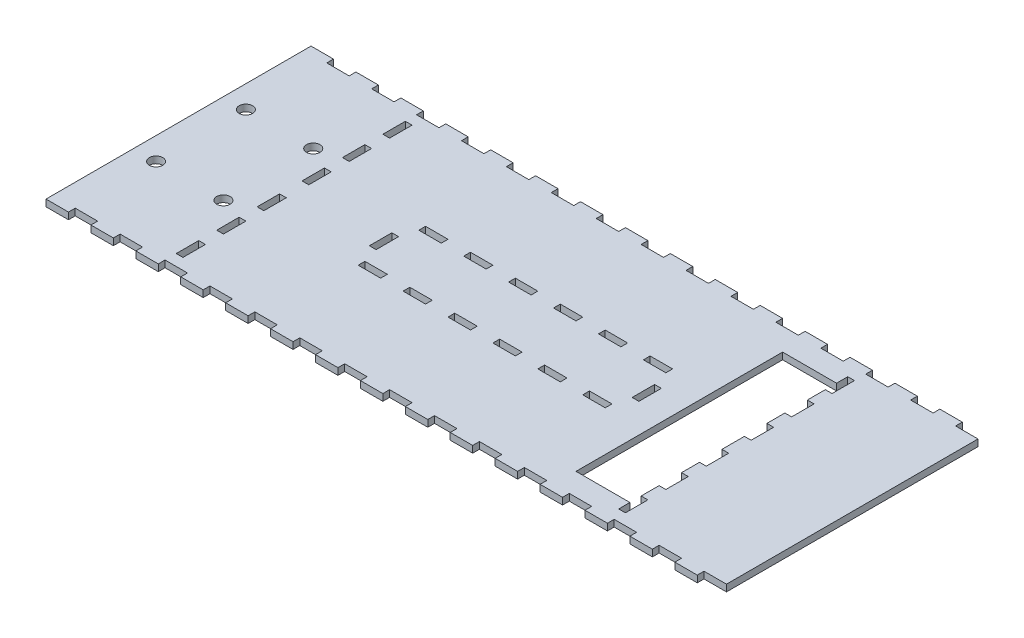
SolidWorks part; units mm, degrees
ref_plane "Front Plane" through (0, 0, 0) normal (0, 0, 1) x (1, 0, 0)
ref_plane "Top Plane" through (0, 0, 0) normal (0, 1, 0) x (1, 0, 0)
ref_plane "Right Plane" through (0, 0, 0) normal (1, 0, 0) x (0, 0, -1)
sketch "Sketch3" plane through (0, 0, 0) normal (0, 1, 0) x (1, 0, 0)
  line L0 (0, 0) -> (-300, 0) construction
  line L1 (-300, -56) -> (-300, 56)
  line L2 (-290, 59) -> (-300, 59)
  line L3 (-290, 56) -> (-290, 59)
  line L4 (-280, 56) -> (-290, 56)
  line L5 (-300, 59) -> (-300, 56)
  line L6 (-270, 59) -> (-280, 59)
  line L7 (-270, 56) -> (-270, 59)
  line L8 (-260, 56) -> (-270, 56)
  line L9 (-280, 59) -> (-280, 56)
  line L10 (-250, 59) -> (-260, 59)
  line L11 (-250, 56) -> (-250, 59)
  line L12 (-240, 56) -> (-250, 56)
  line L13 (-260, 59) -> (-260, 56)
  line L14 (-150, -59) -> (-150, 59) construction
  line L15 (-230, 59) -> (-240, 59)
  line L16 (-230, 56) -> (-230, 59)
  line L17 (-220, 56) -> (-230, 56)
  line L18 (-240, 59) -> (-240, 56)
  line L19 (-210, 59) -> (-220, 59)
  line L20 (-210, 56) -> (-210, 59)
  line L21 (-200, 56) -> (-210, 56)
  line L22 (-10, 59) -> (-20, 59)
  line L23 (0, -56) -> (0, 56)
  line L24 (-10, 56) -> (-10, 59)
  line L25 (-50, -46) -> (-50, 46) construction
  line L26 (-247, 23) -> (-250, 23)
  line L27 (-247, 5) -> (-250, 5)
  line L28 (-247, 48.5) -> (-247, -48.5) construction
  line L29 (-247, 48.5) -> (-223, 48.5) construction
  line L30 (-223, 48.5) -> (-223, -48.5) construction
  line L31 (-210, 15) -> (-90, 15) construction
  line L32 (-90, 15) -> (-90, 5) construction
  line L33 (0, 56) -> (-10, 56)
  line L34 (-220, 59) -> (-220, 56)
  line L35 (-190, 59) -> (-200, 59)
  line L36 (-190, 56) -> (-190, 59)
  line L37 (-180, 56) -> (-190, 56)
  line L38 (-200, 59) -> (-200, 56)
  line L39 (-170, 59) -> (-180, 59)
  line L40 (-170, 56) -> (-170, 59)
  line L41 (-160, 56) -> (-170, 56)
  line L42 (-180, 59) -> (-180, 56)
  line L43 (-150, 59) -> (-160, 59)
  line L44 (-150, 56) -> (-150, 59)
  line L45 (-140, 56) -> (-150, 56)
  line L46 (-160, 59) -> (-160, 56)
  line L47 (-130, 59) -> (-140, 59)
  line L48 (-130, 56) -> (-130, 59)
  line L49 (-120, 56) -> (-130, 56)
  line L50 (-140, 59) -> (-140, 56)
  line L51 (-110, 59) -> (-120, 59)
  line L52 (-110, 56) -> (-110, 59)
  line L53 (-100, 56) -> (-110, 56)
  line L54 (-120, 59) -> (-120, 56)
  line L55 (-90, 59) -> (-100, 59)
  line L56 (-90, 56) -> (-90, 59)
  line L57 (-80, 56) -> (-90, 56)
  line L58 (-100, 59) -> (-100, 56)
  line L59 (-70, 59) -> (-80, 59)
  line L60 (-70, 56) -> (-70, 59)
  line L61 (-60, 56) -> (-70, 56)
  line L62 (-80, 59) -> (-80, 56)
  line L63 (-50, 59) -> (-60, 59)
  line L64 (-50, 56) -> (-50, 59)
  line L65 (-40, 56) -> (-50, 56)
  line L66 (-60, 59) -> (-60, 56)
  line L67 (-30, 59) -> (-40, 59)
  line L68 (-210, -15) -> (-90, -15) construction
  line L69 (-30, 56) -> (-30, 59)
  line L70 (-53, -23) -> (-50, -23)
  line L71 (-20, -59) -> (-20, -56)
  line L72 (-40, -59) -> (-40, -56)
  line L73 (-20, -56) -> (-30, -56)
  line L74 (-30, -56) -> (-30, -59)
  line L75 (-30, -59) -> (-40, -59)
  line L76 (-60, -59) -> (-60, -56)
  line L77 (-40, -56) -> (-50, -56)
  line L78 (-50, -56) -> (-50, -59)
  line L79 (-50, -59) -> (-60, -59)
  line L80 (-80, -59) -> (-80, -56)
  line L81 (-60, -56) -> (-70, -56)
  line L82 (-70, -56) -> (-70, -59)
  line L83 (-70, -59) -> (-80, -59)
  line L84 (-100, -59) -> (-100, -56)
  line L85 (-80, -56) -> (-90, -56)
  line L86 (-90, -56) -> (-90, -59)
  line L87 (-90, -59) -> (-100, -59)
  line L88 (-120, -59) -> (-120, -56)
  line L89 (-100, -56) -> (-110, -56)
  line L90 (-110, -56) -> (-110, -59)
  line L91 (-110, -59) -> (-120, -59)
  line L92 (-140, -59) -> (-140, -56)
  line L93 (-120, -56) -> (-130, -56)
  line L94 (-130, -56) -> (-130, -59)
  line L95 (-130, -59) -> (-140, -59)
  line L96 (-160, -59) -> (-160, -56)
  line L97 (-140, -56) -> (-150, -56)
  line L98 (-150, -56) -> (-150, -59)
  line L99 (-150, -59) -> (-160, -59)
  line L100 (-180, -59) -> (-180, -56)
  line L101 (-160, -56) -> (-170, -56)
  line L102 (-170, -56) -> (-170, -59)
  line L103 (-170, -59) -> (-180, -59)
  line L104 (-200, -59) -> (-200, -56)
  line L105 (-180, -56) -> (-190, -56)
  line L106 (-190, -56) -> (-190, -59)
  line L107 (-190, -59) -> (-200, -59)
  line L108 (-247, -48.5) -> (-223, -48.5) construction
  line L109 (-247, 5) -> (-247, 15)
  line L110 (-220, -59) -> (-220, -56)
  line L111 (0, -56) -> (-10, -56)
  line L112 (-10, -56) -> (-10, -59)
  line L113 (-10, -59) -> (-20, -59)
  line L114 (-200, -56) -> (-210, -56)
  line L115 (-210, -56) -> (-210, -59)
  line L116 (-210, -59) -> (-220, -59)
  line L117 (-240, -59) -> (-240, -56)
  line L118 (-220, -56) -> (-230, -56)
  line L119 (-230, -56) -> (-230, -59)
  line L120 (-230, -59) -> (-240, -59)
  line L121 (-53, -5) -> (-50, -5)
  line L122 (-260, -59) -> (-260, -56)
  line L123 (-240, -56) -> (-250, -56)
  line L124 (-250, -56) -> (-250, -59)
  line L125 (-250, -59) -> (-260, -59)
  line L126 (-280, -59) -> (-280, -56)
  line L127 (-260, -56) -> (-270, -56)
  line L128 (-270, -56) -> (-270, -59)
  line L129 (-270, -59) -> (-280, -59)
  line L130 (-300, -59) -> (-300, -56)
  line L131 (-210, 15) -> (-210, -15) construction
  line L132 (-115, 15) -> (-125, 15)
  line L133 (-90, 5) -> (-93, 5)
  line L134 (-90, 5) -> (-90, -5)
  line L135 (-90, -5) -> (-93, -5)
  line L136 (-93, 5) -> (-93, -5)
  line L137 (-95, 15) -> (-105, 15)
  line L138 (-95, 15) -> (-95, 12)
  line L139 (-95, 12) -> (-105, 12)
  line L140 (-105, 15) -> (-105, 12)
  line L141 (-115, 12) -> (-125, 12)
  line L142 (-125, 15) -> (-125, 12)
  line L143 (-135, 15) -> (-145, 15)
  line L144 (-135, 12) -> (-145, 12)
  line L145 (-145, 15) -> (-145, 12)
  line L146 (-155, 15) -> (-165, 15)
  line L147 (-155, 12) -> (-165, 12)
  line L148 (-165, 15) -> (-165, 12)
  line L149 (-175, 15) -> (-185, 15)
  line L150 (-175, 12) -> (-185, 12)
  line L151 (-185, 15) -> (-185, 12)
  line L152 (-195, 15) -> (-205, 15)
  line L153 (-195, 12) -> (-205, 12)
  line L154 (-205, 15) -> (-205, 12)
  line L155 (-195, 12) -> (-195, 15)
  line L156 (-175, 12) -> (-175, 15)
  line L157 (-155, 12) -> (-155, 15)
  line L158 (-135, 12) -> (-135, 15)
  line L159 (-115, 12) -> (-115, 15)
  line L160 (-207, 5) -> (-207, -5)
  line L161 (-210, -5) -> (-207, -5)
  line L162 (-210, 5) -> (-210, -5)
  line L163 (-210, 5) -> (-207, 5)
  line L164 (-115, -12) -> (-115, -15)
  line L165 (-135, -12) -> (-135, -15)
  line L166 (-155, -12) -> (-155, -15)
  line L167 (-175, -12) -> (-175, -15)
  line L168 (-195, -12) -> (-195, -15)
  line L169 (-205, -15) -> (-205, -12)
  line L170 (-195, -12) -> (-205, -12)
  line L171 (-195, -15) -> (-205, -15)
  line L172 (-185, -15) -> (-185, -12)
  line L173 (-175, -12) -> (-185, -12)
  line L174 (-175, -15) -> (-185, -15)
  line L175 (-165, -15) -> (-165, -12)
  line L176 (-155, -12) -> (-165, -12)
  line L177 (-155, -15) -> (-165, -15)
  line L178 (-145, -15) -> (-145, -12)
  line L179 (-135, -12) -> (-145, -12)
  line L180 (-135, -15) -> (-145, -15)
  line L181 (-125, -15) -> (-125, -12)
  line L182 (-115, -12) -> (-125, -12)
  line L183 (-105, -15) -> (-105, -12)
  line L184 (-95, -12) -> (-105, -12)
  line L185 (-95, -15) -> (-95, -12)
  line L186 (-95, -15) -> (-105, -15)
  line L187 (-115, -15) -> (-125, -15)
  line L188 (-247, 15) -> (-250, 15)
  line L189 (-250, 5) -> (-250, 15)
  line L190 (-247, 23) -> (-247, 33)
  line L191 (-247, 33) -> (-250, 33)
  line L192 (-250, 23) -> (-250, 33)
  line L193 (-247, 41) -> (-250, 41)
  line L194 (-247, 41) -> (-247, 51)
  line L195 (-247, 51) -> (-250, 51)
  line L196 (-250, 41) -> (-250, 51)
  line L197 (-250, -41) -> (-250, -51)
  line L198 (-247, -51) -> (-250, -51)
  line L199 (-247, -41) -> (-247, -51)
  line L200 (-247, -41) -> (-250, -41)
  line L201 (-250, -23) -> (-250, -33)
  line L202 (-247, -33) -> (-250, -33)
  line L203 (-247, -23) -> (-247, -33)
  line L204 (-250, -5) -> (-250, -15)
  line L205 (-247, -15) -> (-250, -15)
  line L206 (-247, -5) -> (-247, -15)
  line L207 (-247, -5) -> (-250, -5)
  line L208 (-247, -23) -> (-250, -23)
  line L209 (-53, -5) -> (-53, -15)
  line L210 (-53, -15) -> (-50, -15)
  line L211 (-50, -5) -> (-50, -15)
  line L212 (-53, -23) -> (-53, -33)
  line L213 (-53, -33) -> (-50, -33)
  line L214 (-50, -23) -> (-50, -33)
  line L215 (-53, -41) -> (-50, -41)
  line L216 (-53, -41) -> (-53, -51)
  line L217 (-53, -51) -> (-50, -51)
  line L218 (-50, -41) -> (-50, -51)
  line L219 (-50, 41) -> (-50, 51)
  line L220 (-53, 51) -> (-50, 51)
  line L221 (-53, 41) -> (-53, 51)
  line L222 (-53, 41) -> (-50, 41)
  line L223 (-50, 23) -> (-50, 33)
  line L224 (-53, 33) -> (-50, 33)
  line L225 (-53, 23) -> (-53, 33)
  line L226 (-50, 5) -> (-50, 15)
  line L227 (-53, 15) -> (-50, 15)
  line L228 (-53, 5) -> (-53, 15)
  line L229 (-53, 5) -> (-50, 5)
  line L230 (-53, 23) -> (-50, 23)
  line L231 (-280, -56) -> (-290, -56)
  line L232 (-290, -56) -> (-290, -59)
  line L233 (-290, -59) -> (-300, -59)
  line L234 (-20, 56) -> (-30, 56)
  line L235 (-40, 59) -> (-40, 56)
  line L236 (-20, 59) -> (-20, 56)
  circle A0 centre (-290, 20) radius 3
  circle A1 centre (-260, 20) radius 3
  circle A2 centre (-260, -20) radius 3
  circle A3 centre (-290, -20) radius 3
  point P80 (-91.5, 0)
  point P82 (-150, 0)
  point P126 (-223, 0)
  point P127 (-250, 0)
  point P129 (-50, 0)
  point P150 (-150, -15)
  point P151 (-150, 15)
  point P183 (-208.5, 0)
  point P212 (-223, 18)
  point P213 (-250, 18)
  point P218 (-223, 36)
  point P219 (-250, 36)
  point P233 (-250, -36)
  point P234 (-250, -18)
  point P257 (-50, -18)
  point P258 (-50, -36)
  point P259 (-50, 36)
  point P260 (-50, 18)
  dimension "D17" = 6
  dimension "D18" = 6
  dimension "D1" = 300
  dimension "D4" = 97
  dimension "D7" = 10
  dimension "D8" = 56
  dimension "D9" = 3
  dimension "D10" = 5
  dimension "D11" = 48.5
  dimension "D12" = 24
  dimension "D13" = 60
  dimension "D14" = 15
  dimension "D15" = 30
  dimension "D16" = 20
  dimension "D29" = 10
  dimension "D30" = 3
  dimension "D31" = 10
  dimension "D32" = 3
  dimension "D33" = 10
  dimension "D34" = 5
  dimension "D37" = 3
  dimension "D38" = 15
  dimension "D35" = 6
  dimension "D36" = 3
extrude "Boss-Extrude1" add sketch "Sketch3" along normal blind 3 contours L1 L116 L115 L107 L106 L83 L82 L79 L74 L75 L95 L98 L99 L91 L90 L86 region at (-149.7132, 0, 0)
sketch "Sketch4" plane through (0, 3, 0) normal (0, 1, 0) x (1, 0, 0)
  line L0 (-53, 5) -> (-53, 15) construction
  line L1 (-53, 46) -> (-77, 46)
  line L2 (-53, 46) -> (-53, -46)
  line L3 (-53, -46) -> (-77, -46)
  line L4 (-77, 46) -> (-77, -46)
  line L5 (-90, 0) -> (0, 0) construction
  line L6 (-90, 5) -> (-90, -5) construction
  dimension "D1" = 92
  dimension "D2" = 24
  dimension "D3" = 46
extrude "Cut-Extrude1" cut sketch "Sketch4" against normal blind 10
